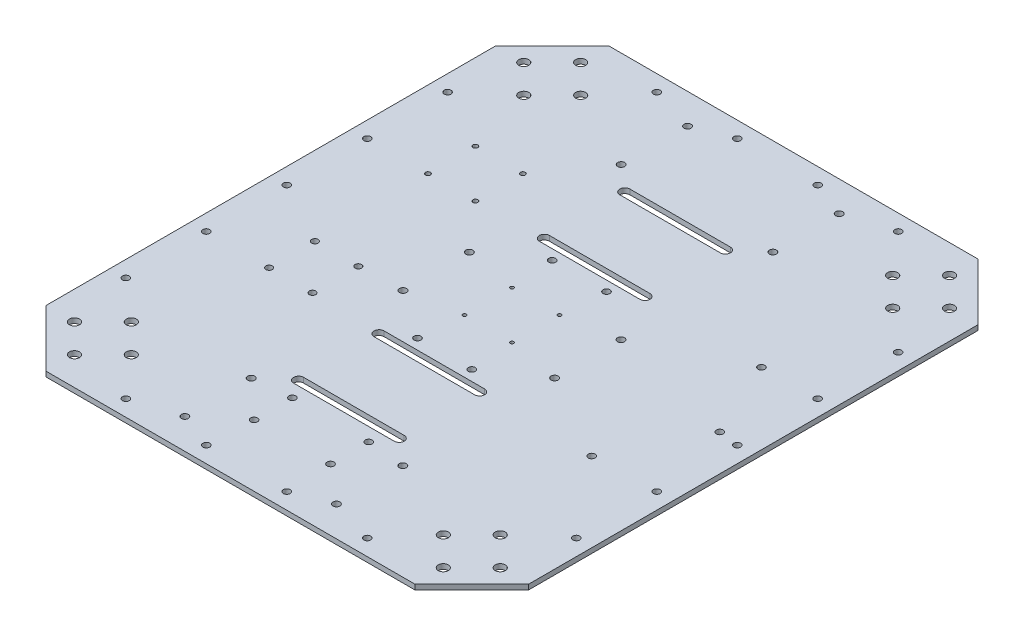
SolidWorks part; units mm, degrees
ref_plane "Front Plane" through (0, 0, 0) normal (0, 0, 1) x (1, 0, 0)
ref_plane "Top Plane" through (0, 0, 0) normal (0, 1, 0) x (1, 0, 0)
ref_plane "Right Plane" through (0, 0, 0) normal (1, 0, 0) x (0, 0, -1)
sketch "Sketch1" plane through (0, 0, 0) normal (0, 1, 0) x (1, 0, 0)
  line L0 (-121.2861, 87.138) -> (-85.365, 123.059)
  line L1 (-121.2861, 123.059) -> (183.5139, 123.059)
  line L2 (-121.2861, 123.059) -> (-121.2861, -232.541)
  line L3 (-121.2861, -232.541) -> (183.5139, -232.541)
  line L4 (183.5139, 123.059) -> (183.5139, -232.541)
  line L5 (31.1139, 95.069) -> (31.1139, -294.9418) construction
  line L6 (-146.0448, -54.741) -> (218.038, -54.741) construction
  line L7 (183.5139, 87.138) -> (147.5929, 123.059)
  line L8 (183.5139, -196.62) -> (147.5929, -232.541)
  line L9 (-121.2861, -196.62) -> (-85.365, -232.541)
  circle A0 centre (-16.7651, 104.009) radius 2.2225
  circle A1 centre (78.9929, 104.009) radius 2.2225
  circle A2 centre (-16.7651, 62.099) radius 2.2225
  circle A3 centre (78.9929, 62.099) radius 2.2225
  circle A4 centre (-16.7651, -171.581) radius 2.2225
  circle A5 centre (78.9929, -171.581) radius 2.2225
  circle A6 centre (78.9929, -213.491) radius 2.2225
  circle A7 centre (-16.7651, -213.491) radius 2.2225
  circle A8 centre (-16.7651, -33.786) radius 2.2225
  circle A9 centre (78.9929, -33.786) radius 2.2225
  circle A10 centre (78.9929, -75.696) radius 2.2225
  circle A11 centre (-16.7651, -75.696) radius 2.2225
  point P8 (31.1139, 123.059)
  point P11 (-121.2861, -54.741)
  dimension "D6" = 95.758
  dimension "D13" = 4.445
  dimension "D1" = 304.8
  dimension "D2" = 355.6
  dimension "D3" = 45
  dimension "D4" = 50.8
  dimension "D5" = 41.91
  dimension "D7" = 104.521
  dimension "D8" = 19.05
  dimension "D9" = 41.91
  dimension "D10" = 20.955
  dimension "D11" = 95.758
  dimension "D12" = 47.879
extrude "Boss-Extrude1" add sketch "Sketch1" along normal blind 3.175 contours L2 L9 L3 L8 L4 L7 L1 L0 region at (31.1139, 0, 54.741)
sketch "Sketch2" plane through (0, 3.175, 0) normal (0, 1, 0) x (1, 0, 0)
  line L0 (31.1139, 123.059) -> (31.1139, -287.8465) construction
  line L1 (-85.365, 123.059) -> (147.5929, 123.059) construction
  line L2 (183.5139, -54.741) -> (-158.2106, -54.741) construction
  line L3 (183.5139, 87.138) -> (183.5139, -196.62) construction
  circle A0 centre (13.8419, -12.069) radius 2.159
  circle A1 centre (48.1319, -12.069) radius 2.159
  circle A2 centre (13.8419, -97.159) radius 2.159
  circle A3 centre (48.1319, -97.159) radius 2.159
  dimension "D5" = 4.318
  dimension "D6" = 4.318
  dimension "D7" = 4.318
  dimension "D8" = 4.318
  dimension "D1" = 17.272
  dimension "D2" = 34.29
  dimension "D3" = 85.09
  dimension "D4" = 42.672
extrude "Cut-Extrude1" cut sketch "Sketch2" against normal through all
sketch "Sketch4" plane through (0, 3.175, 0) normal (0, 1, 0) x (1, 0, 0)
  line L0 (-0.6361, 48.256) -> (62.8639, 48.256) construction
  line L1 (-0.6361, 51.431) -> (62.8639, 51.431)
  line L2 (-0.6361, 45.081) -> (62.8639, 45.081)
  line L3 (-0.6361, -2.544) -> (62.8639, -2.544) construction
  line L4 (-0.6361, 0.631) -> (62.8639, 0.631)
  line L5 (-0.6361, -5.719) -> (62.8639, -5.719)
  line L6 (31.1139, 123.059) -> (31.1139, -75.2432) construction
  line L7 (-85.365, 123.059) -> (147.5929, 123.059) construction
  line L8 (-121.2861, -54.741) -> (257.7387, -54.741) construction
  line L9 (-121.2861, 87.138) -> (-121.2861, -196.62) construction
  line L10 (31.1139, -232.541) -> (31.1139, -34.2388) construction
  line L11 (-0.6361, -106.938) -> (62.8639, -106.938) construction
  line L12 (-0.6361, -110.113) -> (62.8639, -110.113)
  line L13 (-0.6361, -103.763) -> (62.8639, -103.763)
  line L14 (-0.6361, -157.738) -> (62.8639, -157.738) construction
  line L15 (-0.6361, -160.913) -> (62.8639, -160.913)
  line L16 (-0.6361, -154.563) -> (62.8639, -154.563)
  arc A0 (-0.6361, 51.431) -> (-0.6361, 45.081) centre (-0.6361, 48.256) ccw
  arc A1 (62.8639, 45.081) -> (62.8639, 51.431) centre (62.8639, 48.256) ccw
  arc A2 (-0.6361, 0.631) -> (-0.6361, -5.719) centre (-0.6361, -2.544) ccw
  arc A3 (62.8639, -5.719) -> (62.8639, 0.631) centre (62.8639, -2.544) ccw
  circle A4 centre (48.1319, -12.069) radius 2.159 construction
  arc A5 (-0.6361, -110.113) -> (-0.6361, -103.763) centre (-0.6361, -106.938) cw
  arc A6 (62.8639, -103.763) -> (62.8639, -110.113) centre (62.8639, -106.938) cw
  arc A7 (-0.6361, -160.913) -> (-0.6361, -154.563) centre (-0.6361, -157.738) cw
  arc A8 (62.8639, -154.563) -> (62.8639, -160.913) centre (62.8639, -157.738) cw
  point P2 (31.1139, 48.256)
  point P7 (31.1139, -2.544)
  point P28 (31.1139, -106.938)
  point P35 (31.1139, -157.738)
  dimension "D1" = 63.5
  dimension "D2" = 63.5
  dimension "D3" = 6.35
  dimension "D4" = 6.35
  dimension "D5" = 44.45
  dimension "D6" = 6.35
extrude "Cut-Extrude2" cut sketch "Sketch4" against normal through all
sketch "Sketch7" plane through (0, 3.175, 0) normal (0, 1, 0) x (1, 0, 0)
  line L0 (-57.7861, 57.7696) -> (-57.7861, -55.8318) construction
  line L1 (-121.2861, -54.741) -> (183.5139, -54.741) construction
  line L2 (-121.2861, 87.138) -> (-121.2861, -196.62) construction
  line L3 (183.5139, 87.138) -> (183.5139, -196.62) construction
  circle A0 centre (-42.8001, 26.031) radius 1.524
  circle A1 centre (-42.8001, -3.941) radius 1.524
  circle A2 centre (-72.7721, -3.941) radius 1.524
  circle A3 centre (-72.7721, 26.031) radius 1.524
  dimension "D1" = 3.048
  dimension "D2" = 14.986
  dimension "D4" = 29.972
  dimension "D3" = 3.048
  dimension "D5" = 50.8
  dimension "D6" = 63.5
  dimension "D7" = 14.986
extrude "Cut-Extrude3" cut sketch "Sketch7" against normal through all
sketch "Sketch8" plane through (0, 3.175, 0) normal (0, 1, 0) x (1, 0, 0)
  line L0 (-85.365, -232.541) -> (147.5929, -232.541) construction
  line L1 (183.5139, 87.138) -> (183.5139, -196.62) construction
  circle A0 centre (73.0239, -207.649) radius 1.524
  circle A1 centre (73.0239, -177.169) radius 1.524
  circle A2 centre (96.8999, -207.649) radius 1.524
  circle A3 centre (96.8999, -177.169) radius 1.524
  dimension "D1" = 3.048
  dimension "D2" = 30.48
  dimension "D3" = 23.876
  dimension "D4" = 24.892
  dimension "D5" = 86.614
extrude "Cut-Extrude4" [suppressed] cut sketch "Sketch8" against normal through all and the other way through all
sketch "Sketch10" plane through (0, 0, 0) normal (0, -1, 0) x (1, 0, 0)
  line L0 (-85.365, 232.541) -> (147.5929, 232.541) construction
  line L1 (31.1139, 232.541) -> (31.1139, 128.7119) construction
  circle A0 centre (6.9839, 193.4758) radius 2.159
  circle A1 centre (55.2439, 193.4758) radius 2.159
  circle A2 centre (6.9839, 169.3458) radius 2.159
  circle A3 centre (55.2439, 169.3458) radius 2.159
  dimension "D1" = 4.318
  dimension "D2" = 48.26
  dimension "D4" = 39.0652
  dimension "D6" = 4.318
  dimension "D7" = 4.318
  dimension "D8" = 4.318
  dimension "D3" = 24.13
  dimension "D5" = 24.13
extrude "Cut-Extrude6" cut sketch "Sketch10" against normal through all
sketch "Sketch9" plane through (0, 0, 0) normal (0, -1, 0) x (-1, 0, 0)
  line L0 (85.365, -232.541) -> (-147.5929, -232.541) construction
  line L2 (57.7861, -47.3693) -> (57.7861, -130.2963) construction
  line L3 (-147.5929, -232.541) -> (-183.5139, -196.62) construction
  line L4 (-147.5929, -232.541) -> (-111.6719, -196.62) construction
  line L5 (-111.6719, -196.62) -> (-147.5929, -160.699) construction
  line L6 (-183.5139, -196.62) -> (-147.5929, -160.699) construction
  line L7 (121.2861, 87.138) -> (121.2861, -196.62) construction
  line L8 (-183.5139, -196.62) -> (-147.5929, -232.541) construction
  circle A0 centre (71.5021, -105.541) radius 2.032
  circle A1 centre (44.0701, -105.541) radius 2.032
  circle A2 centre (71.5021, -76.585) radius 2.032
  circle A3 centre (44.0701, -76.585) radius 2.032
  point P21 (0, 0)
  dimension "D1" = 4.064
  dimension "D9" = 4.064
  dimension "D2" = 63.5
  dimension "D3" = 28.956
  dimension "D4" = 127
  dimension "D6" = 50.8
  dimension "D7" = 50.8
  dimension "D8" = 13.716
extrude "Cut-Extrude5" cut sketch "Sketch9" against normal through all
sketch "Sketch13" plane through (0, 0, 0) normal (0, -1, 0) x (1, 0, 0)
  line L0 (31.1139, -123.059) -> (31.1139, 261.4711) construction
  line L1 (-85.365, -123.059) -> (147.5929, -123.059) construction
  line L2 (-121.2861, 54.741) -> (239.2508, 54.741) construction
  line L3 (-121.2861, -87.138) -> (-121.2861, 196.62) construction
  circle A0 centre (16.1139, 69.741) radius 1.1
  circle A1 centre (16.1139, 39.741) radius 1.1
  circle A2 centre (46.1139, 39.741) radius 1.1
  circle A3 centre (46.1139, 69.741) radius 1.1
  dimension "D1" = 2.2
  dimension "D2" = 2.2
  dimension "D3" = 30
  dimension "D4" = 15
  dimension "D5" = 15
extrude "Cut-Extrude8" cut sketch "Sketch13" against normal through all
sketch "Sketch14" plane through (0, 0, 0) normal (0, -1, 0) x (1, 0, 0)
  line L0 (31.1139, 232.541) -> (31.1139, -154.5354) construction
  line L1 (-85.365, 232.541) -> (147.5929, 232.541) construction
  line L2 (-121.2861, 54.741) -> (331.9066, 54.741) construction
  line L3 (-121.2861, -87.138) -> (-121.2861, 196.62) construction
  line L4 (-85.365, 214.5805) -> (-103.3255, 196.62) construction
  line L5 (-103.3255, 196.62) -> (-85.365, 178.6595) construction
  line L6 (-85.365, 178.6595) -> (-67.4045, 196.62) construction
  line L7 (-67.4045, 196.62) -> (-85.365, 214.5805) construction
  line L8 (-121.2861, 196.62) -> (-85.365, 232.541) construction
  line L9 (-103.3255, 214.5805) -> (-48.3665, 159.6215) construction
  circle A0 centre (-103.3255, 196.62) radius 3.175
  circle A1 centre (-85.365, 214.5805) radius 3.175
  circle A2 centre (-85.365, 178.6595) radius 3.175
  circle A3 centre (-67.4045, 196.62) radius 3.175
  circle A4 centre (129.6324, 196.62) radius 3.175
  circle A5 centre (147.5929, 178.6595) radius 3.175
  circle A6 centre (165.5534, 196.62) radius 3.175
  circle A7 centre (147.5929, 214.5805) radius 3.175
  circle A8 centre (-85.365, -105.0985) radius 3.175
  circle A9 centre (-103.3255, -87.138) radius 3.175
  circle A10 centre (-85.365, -69.1774) radius 3.175
  circle A11 centre (-67.4045, -87.138) radius 3.175
  circle A12 centre (165.5534, -87.138) radius 3.175
  circle A13 centre (147.5929, -69.1774) radius 3.175
  circle A14 centre (147.5929, -105.0985) radius 3.175
  circle A15 centre (129.6324, -87.138) radius 3.175
  dimension "D3" = 6.35
  dimension "D4" = 6.35
  dimension "D5" = 6.35
  dimension "D6" = 6.35
  dimension "D2" = 12.7
  dimension "D7" = 90
  dimension "D8" = 25.4
  dimension "D9" = 25.4
  dimension "D10" = 12.7
  dimension "D11" = 90
extrude "Cut-Extrude9" cut sketch "Sketch14" against normal through all
sketch "Sketch15" plane through (0, 0, 0) normal (0, -1, 0) x (1, 0, 0)
  line L0 (31.1139, 232.541) -> (31.1139, 125.875) construction
  line L1 (-85.365, 232.541) -> (147.5929, 232.541) construction
  line L2 (-121.2861, 54.741) -> (75.4631, 54.741) construction
  line L3 (-121.2861, -87.138) -> (-121.2861, 196.62) construction
  circle A0 centre (5.7139, 222.381) radius 2.159
  circle A1 centre (-45.0861, 222.381) radius 2.159
  circle A2 centre (-111.1261, 54.741) radius 2.159
  circle A3 centre (-111.1261, 105.541) radius 2.159
  circle A4 centre (-111.1261, 156.341) radius 2.159
  circle A5 centre (173.3539, 156.341) radius 2.159
  circle A6 centre (173.3539, 105.541) radius 2.159
  circle A7 centre (173.3539, 54.741) radius 2.159
  circle A8 centre (107.3139, 222.381) radius 2.159
  circle A9 centre (56.5139, 222.381) radius 2.159
  circle A10 centre (56.5139, -112.899) radius 2.159
  circle A11 centre (107.3139, -112.899) radius 2.159
  circle A12 centre (173.3539, 3.941) radius 2.159
  circle A13 centre (173.3539, -46.859) radius 2.159
  circle A14 centre (-111.1261, -46.859) radius 2.159
  circle A15 centre (-111.1261, 3.941) radius 2.159
  circle A16 centre (-45.0861, -112.899) radius 2.159
  circle A17 centre (5.7139, -112.899) radius 2.159
  dimension "D3" = 4.318
  dimension "D4" = 4.318
  dimension "D8" = 4.318
  dimension "D9" = 4.318
  dimension "D10" = 4.318
  dimension "D1" = 25.4
  dimension "D2" = 50.8
  dimension "D5" = 10.16
  dimension "D6" = 50.8
  dimension "D7" = 50.8
  dimension "D11" = 10.16
extrude "Cut-Extrude10" cut sketch "Sketch15" against normal through all
sketch "Sketch16" plane through (0, 0, 0) normal (0, -1, 0) x (-1, 0, 0)
  line L1 (-103.7737, -99.6794) -> (-153.6537, -99.6794)
  line L2 (-103.7737, -99.6794) -> (-103.7737, -11.5294)
  line L3 (-103.7737, -11.5294) -> (-153.6537, -11.5294)
  line L4 (-153.6537, -99.6794) -> (-153.6537, -11.5294)
  line L5 (-183.5139, 87.138) -> (-183.5139, -196.62) construction
  circle A0 centre (-133.3337, -106.6794) radius 2.159
  circle A1 centre (-138.4137, -4.5294) radius 2.159
  circle A2 centre (-160.6539, -53.0294) radius 2.159
  dimension "D3" = 7
  dimension "D4" = 7.0002
  dimension "D5" = 7
  dimension "D6" = 20.32
  dimension "D7" = 15.24
  dimension "D8" = 46.65
  dimension "D9" = 4.318
  dimension "D10" = 4.318
  dimension "D11" = 4.318
  dimension "D1" = 88.15
  dimension "D2" = 49.88
  dimension "D12" = 22.86
extrude "Cut-Extrude11" cut sketch "Sketch16" against normal through all contours A2 | A0 | A1
